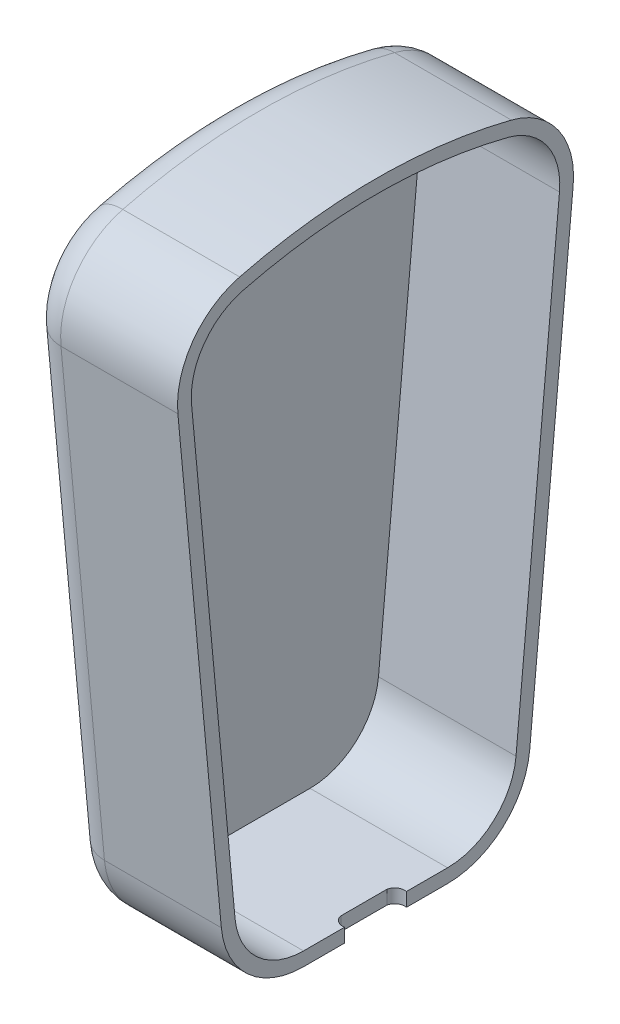
SolidWorks part; units mm, degrees
ref_plane "Front Plane" through (0, 0, 0) normal (0, 0, 1) x (1, 0, 0)
ref_plane "Top Plane" through (0, 0, 0) normal (0, 1, 0) x (1, 0, 0)
ref_plane "Right Plane" through (0, 0, 0) normal (1, 0, 0) x (0, 0, -1)
sketch "Sketch2" plane through (0, 0, 0) normal (1, 0, 0) x (0, 0, -1)
  line L0 (0, 0) -> (0, 38.9444) construction
  line L1 (0, 38.9444) -> (0, -46.0556) construction
  line L2 (27.5, 38.9444) -> (-27.5, 38.9444) construction
  line L3 (15, -46.0556) -> (-15, -46.0556) construction
  line L4 (-6.5405, 38.9444) -> (-6.5405, -15.0556) construction
  line L5 (22.5, -15.0556) -> (-22.5, -15.0556) construction
  line L6 (-26.7525, 30.9147) -> (-20.4317, -36.9825)
  line L7 (26.7525, 30.9147) -> (20.4317, -36.9825)
  line L8 (-10.4748, -46.0556) -> (10.4748, -46.0556)
  line L9 (0, 38.9444) -> (-22.5, 38.9444) construction
  arc A0 (-19.2609, 41.5329) -> (19.2609, 41.5329) centre (0, -34.1806) cw
  arc A1 (-19.2609, 41.5329) -> (-26.7525, 30.9147) centre (-16.7955, 31.8416) ccw
  arc A2 (19.2609, 41.5329) -> (26.7525, 30.9147) centre (16.7955, 31.8416) cw
  arc A3 (-10.4748, -46.0556) -> (-20.4317, -36.9825) centre (-10.4748, -36.0556) cw
  arc A4 (20.4317, -36.9825) -> (10.4748, -46.0556) centre (10.4748, -36.0556) cw
  point P12 (0, -15.0556)
  point P14 (0, 43.9444)
  point P26 (-19.5871, -46.0556)
  point P29 (19.5871, -46.0556)
  dimension "D6" = 5
  dimension "D7" = 10
  dimension "D8" = 10
  dimension "D9" = 10
  dimension "D10" = 10
  dimension "D1" = 85
  dimension "D2" = 27.5
  dimension "D3" = 15
  dimension "D4" = 54
  dimension "D5" = 22.5
extrude "Boss-Extrude1" add sketch "Sketch2" along normal blind 20
shell "Shell4" thickness 2 removed face at (20, -2.4825, 0) outward yes
fillet "Fillet2" radius 5 8 edges at (-2, 45.9444, 0) (-2, 38.7595, -26.6008) (-2, -3.2193, -25.5835) (-2, -44.9254, -18.5572) (-2, -48.0556, 0) (-2, -44.9254, 18.5572) (-2, -3.2193, 25.5835) (-2, 38.7595, 26.6008)
sketch "Sketch3" plane through (0, -48.0556, 0) normal (0, -1, 0) x (1, 0, 0)
  line L0 (20, -4.5) -> (20, 4.5)
  line L1 (20, 10.4748) -> (20, -10.4748) construction
  line L2 (20, 0) -> (18.3, 0) construction
  line L3 (18.3, -3.345) -> (18.3, 3.345)
  arc A0 (18.3, 3.345) -> (20, 4.5) centre (19.7275, 3.0725) cw
  arc A1 (18.3, -3.345) -> (20, -4.5) centre (19.7275, -3.0725) ccw
  dimension "D1" = 4.5
  dimension "D2" = 1.7
  dimension "D3" = 3.345
extrude "Cut-Extrude1" cut sketch "Sketch3" against normal up to surface (2 mm away) up to face at (10, -46.0556, 0)
